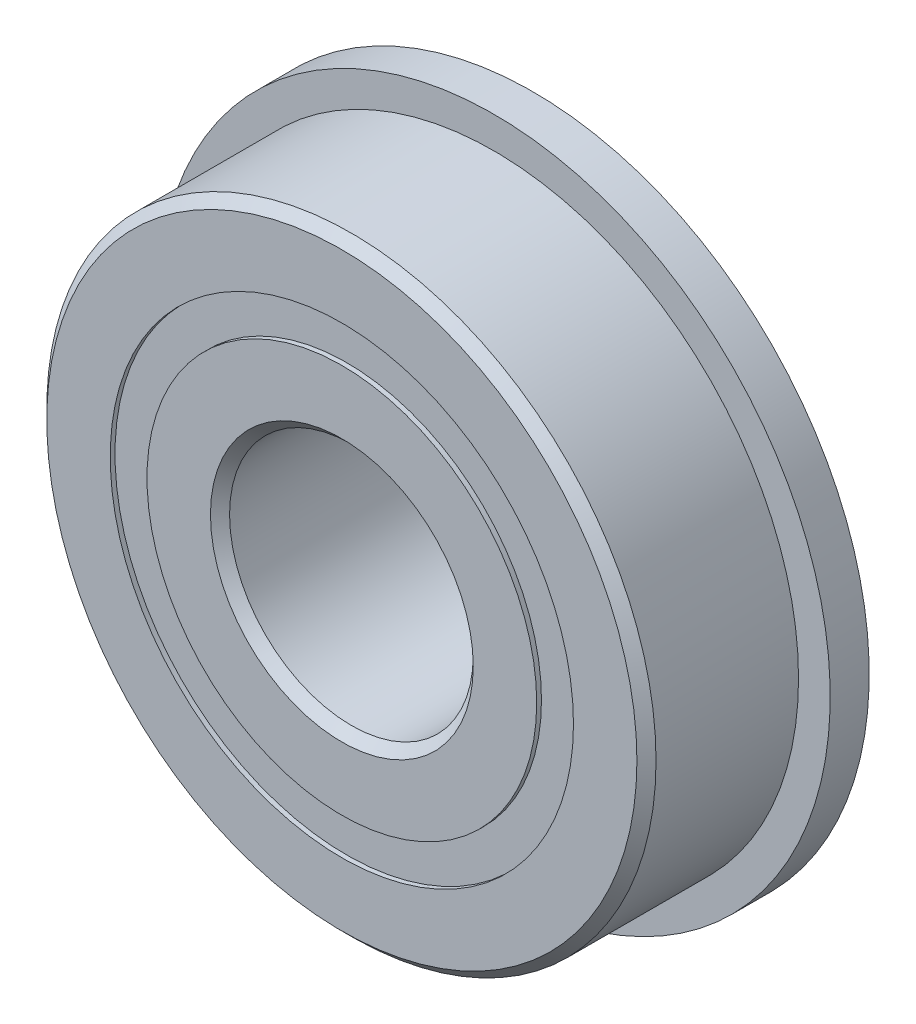
SolidWorks part; units mm, degrees
ref_plane "Front Plane" through (0, 0, 0) normal (0, 0, 1) x (1, 0, 0)
ref_plane "Top Plane" through (0, 0, 0) normal (0, 1, 0) x (1, 0, 0)
ref_plane "Right Plane" through (0, 0, 0) normal (1, 0, 0) x (0, 0, -1)
sketch "Sketch1" plane through (0, 0, 0) normal (1, 0, 0) x (0, 0, -1)
  line L0 (-2.4892, 0) -> (2.4892, 0) construction
  line L1 (0, 7.9375) -> (0, -7.9375) construction
  line L2 (2.2403, 7.9375) -> (-2.2403, 7.9375)
  line L3 (-2.2403, 7.9375) -> (-2.4892, 7.6886)
  line L4 (-2.4892, 7.6886) -> (-2.4892, 6.0352)
  line L5 (-2.4892, 6.0352) -> (-1.1063, 6.0352)
  line L6 (2.4892, 6.0352) -> (1.1063, 6.0352)
  line L7 (2.4892, 7.6886) -> (2.4892, 6.0352)
  line L8 (2.2403, 7.9375) -> (2.4892, 7.6886)
  line L9 (0, 7.9375) -> (0, 5.5563) construction
  line L10 (0, 5.5563) -> (0, 3.175) construction
  arc A0 (-1.1063, 6.0352) -> (1.1063, 6.0352) centre (0, 5.5563) cw
  point P14 (0, 3.175)
  dimension "Width" = 4.9784
  dimension "OD" = 15.875
  dimension "D1" = 45
  dimension "D2" = 0.2489
  dimension "Shaft Dia" = 6.35
  dimension "D3" = 2.2126
  dimension "D4" = 0.479
revolve "Revolve1" add sketch "Sketch1" angle 360 about L0
sketch "Sketch3" plane through (0, 0, 0) normal (1, 0, 0) x (0, 0, -1)
  line L0 (-2.4892, 5.0773) -> (-1.1063, 5.0773)
  line L1 (0, 7.9375) -> (0, -7.9375) construction
  line L2 (-2.4892, 7.6886) -> (-2.4892, 6.0352) construction
  line L3 (-2.4892, 5.0773) -> (-2.4892, 3.4239)
  line L4 (-2.2403, 7.9375) -> (-2.4892, 7.6886) construction
  line L5 (-2.4892, 3.4239) -> (-2.2403, 3.175)
  line L6 (-2.2403, 3.175) -> (2.2403, 3.175)
  line L7 (2.2403, 7.9375) -> (2.2403, -7.9375) construction
  line L8 (2.2403, 3.175) -> (2.4892, 3.4239)
  line L9 (2.4892, -7.6886) -> (2.4892, 7.6886) construction
  line L10 (2.4892, 3.4239) -> (2.4892, 5.0773)
  line L11 (2.4892, 5.0773) -> (1.1063, 5.0773)
  line L13 (2.2403, 7.9375) -> (2.4892, 7.6886) construction
  arc A0 (1.1063, 6.0352) -> (-1.1063, 6.0352) centre (0, 5.5563) ccw construction
  arc A1 (1.1063, 5.0773) -> (-1.1063, 5.0773) centre (0, 5.5562) cw
revolve "Revolve3" add sketch "Sketch3" angle 360 about L0
sketch "Sketch4" plane through (0, 0, 0) normal (1, 0, 0) x (0, 0, -1)
  line L0 (-1.2055, 5.5563) -> (1.2055, 5.5563)
  arc A2 (-1.2055, 5.5563) -> (1.2055, 5.5563) centre (0, 5.5563) cw
  arc A3 (1.1063, 6.0352) -> (-1.1063, 6.0352) centre (0, 5.5563) ccw construction
revolve "Revolve4" add sketch "Sketch4" angle 360 about L0
ref_axis "Axis1" through (0, 0, -2.4892) along (0, 0, 1)
pattern_circular "CirPattern1" count 12 every 30 about axis through (0, 0, -2.4892) along (0, 0, 1) of bodies 104
sketch "Sketch5" plane through (0, 0, 0) normal (1, 0, 0) x (0, 0, -1)
  line L0 (-2.4892, 6.0352) -> (-1.1063, 6.0352) construction
  line L1 (-2.3647, 6.0352) -> (-1.2055, 6.0352)
  line L2 (-2.3647, 6.0352) -> (-2.3647, 5.0773)
  line L3 (-2.3647, 5.0773) -> (-1.2055, 5.0773)
  line L4 (-1.2055, 6.0352) -> (-1.2055, 5.0773)
  line L5 (-2.4892, 5.0773) -> (-1.1063, 5.0773) construction
  line L6 (2.4892, 6.0352) -> (1.1063, 6.0352) construction
  line L7 (2.3647, 6.0352) -> (1.2055, 6.0352)
  line L8 (2.3647, 6.0352) -> (2.3647, 5.0773)
  line L9 (2.3647, 5.0773) -> (1.2055, 5.0773)
  line L10 (1.2055, 6.0352) -> (1.2055, 5.0773)
  line L11 (2.4892, 5.0773) -> (1.1063, 5.0773) construction
  line L12 (-2.2403, 7.9375) -> (-2.4892, 7.6886) construction
  point P18 (-2.3647, 7.813)
revolve "Revolve5" add sketch "Sketch5" angle 360 about L0
sketch "Sketch6" plane through (0, 0, 0) normal (1, 0, 0) x (0, 0, -1)
  line L0 (2.4892, 0) -> (-2.4892, 0) construction
  line L1 (2.4892, 6.0352) -> (1.4732, 6.0352)
  line L2 (2.4892, 6.0352) -> (2.4892, 8.763)
  line L3 (2.4892, 8.763) -> (1.4732, 8.763)
  line L4 (1.4732, 6.0352) -> (1.4732, 8.763)
  dimension "Th" = 1.016
  dimension "Flange OD" = 17.526
revolve "Revolve6" add sketch "Sketch6" angle 360 about L0
equation "\"D2@Sketch1\" = \"Width@Sketch1\"*.05"
equation "\"D3@Sketch1\" = \"Width@Sketch1\"/2.25"
equation "\"D4@Sketch1\" = (((\"OD@Sketch1\"-\"Width@Sketch1\")/2)/3.25)/3.5"
equation "\"D2@CirPattern1\" = 360/\"Balls@CirPattern1\""
